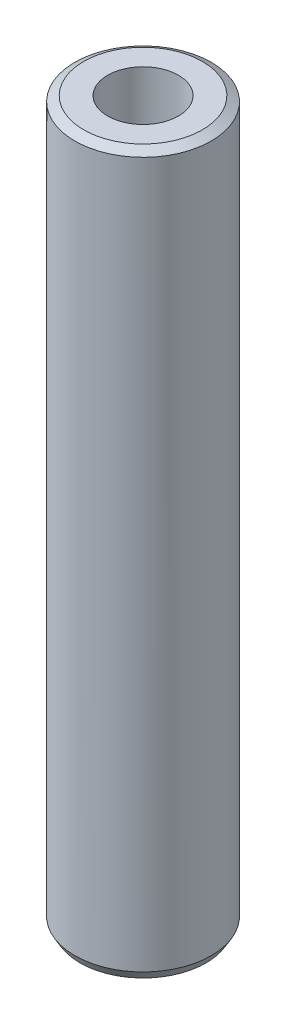
SolidWorks part; units mm, degrees
ref_plane "Front Plane" through (0, 0, 0) normal (0, 0, 1) x (1, 0, 0)
ref_plane "Top Plane" through (0, 0, 0) normal (0, 1, 0) x (1, 0, 0)
ref_plane "Right Plane" through (0, 0, 0) normal (1, 0, 0) x (0, 0, -1)
sketch "Sketch1" plane through (0, 0, 0) normal (0, 1, 0) x (1, 0, 0)
  circle A0 centre (0, 0) radius 37.5
  dimension "SHAFT_OD" = 75
extrude "Boss-Extrude1" add sketch "Sketch1" along normal blind 395.5856
sketch "Sketch2" plane through (0, 0, 0) normal (0, 1, 0) x (1, 0, 0)
  circle A0 centre (0, 0) radius 19.4556
  dimension "BORE_D" = 38.9112
extrude "Cut-Extrude1" cut sketch "Sketch2" along normal through all
chamfer "Chamfer1" distance 2.8608 angle 59.73 2 edges at (0, 395.5856, 37.5) (0, 0, 37.5) first distance on face at (0, 395.5856, 37.5) first distance on face at (0, 0, 19.4556)
